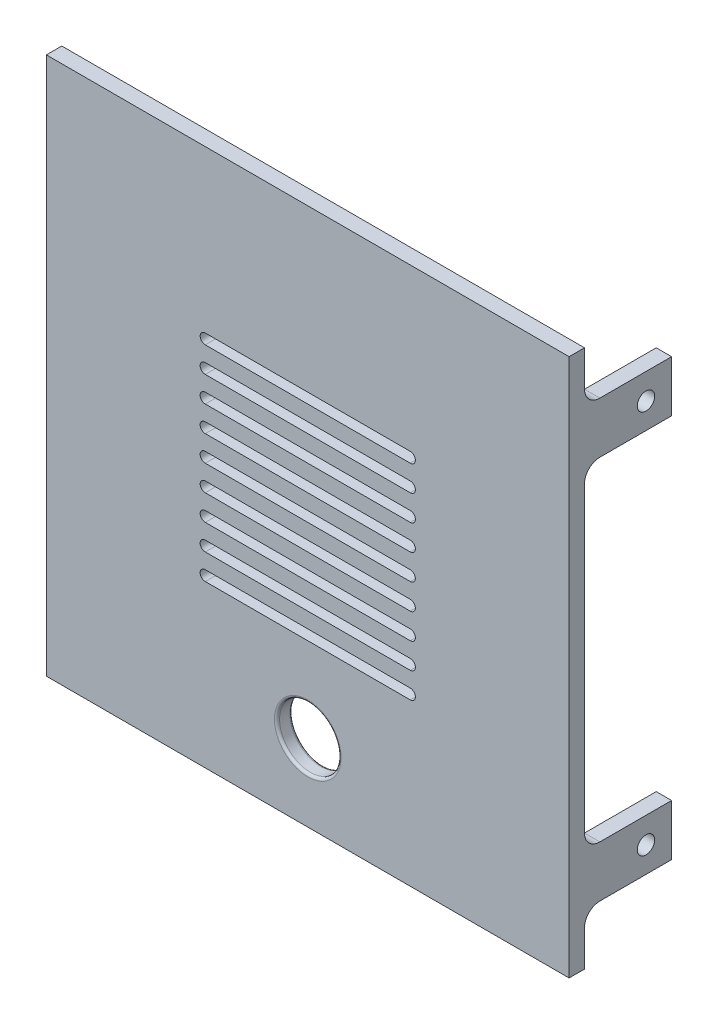
SolidWorks part; units mm, degrees
ref_plane "Front Plane" through (0, 0, 0) normal (0, 0, 1) x (1, 0, 0)
ref_plane "Top Plane" through (0, 0, 0) normal (0, 1, 0) x (1, 0, 0)
ref_plane "Right Plane" through (0, 0, 0) normal (1, 0, 0) x (0, 0, -1)
sketch "Sketch1" plane through (0, 0, 0) normal (0, 0, 1) x (1, 0, 0)
  line L1 (51, 52.5) -> (-51, 52.5)
  line L2 (51, 52.5) -> (51, -52.5)
  line L3 (51, -52.5) -> (-51, -52.5)
  line L4 (-51, 52.5) -> (-51, -52.5)
  line L5 (51, 52.5) -> (-51, -52.5) construction
  line L6 (51, -52.5) -> (-51, 52.5) construction
  point P0 (0, 0)
  dimension "D1" = 105
  dimension "D2" = 102
extrude "Boss-Extrude1" add sketch "Sketch1" along normal mid plane 3
sketch "Sketch2" plane through (0, 0, -1.5) normal (0, 0, -1) x (-1, 0, 0)
  line L1 (41.07, -29.23) -> (44.07, -29.23)
  line L2 (41.07, -29.23) -> (41.07, -39.23)
  line L3 (41.07, -39.23) -> (44.07, -39.23)
  line L4 (44.07, -29.23) -> (44.07, -39.23)
  line L5 (41.07, -29.23) -> (44.07, -39.23) construction
  line L6 (41.07, -39.23) -> (44.07, -29.23) construction
  line L8 (51, -52.5) -> (-51, -52.5) construction
  line L9 (51, 52.5) -> (51, -52.5) construction
  point P0 (42.57, -34.23)
  dimension "D1" = 10
  dimension "D2" = 3
  dimension "D3" = 18.27
  dimension "D4" = 6.93
extrude "Boss-Extrude2" add sketch "Sketch2" along normal blind 23
fillet "Fillet1" radius 2 2 edges at (-41.07, -34.23, -1.5) (-44.07, -34.23, -1.5)
hole_wizard "M3 Clearance Hole1" positions "Sketch3" profile "Sketch5" hole size "M3" standard "ISO" end condition through all
sketch "Sketch3" plane through (-44.07, 0, 0) normal (-1, 0, 0) x (0, 0, 1)
  line L1 (-1.5, 52.5) -> (-1.5, -52.5) construction
  line L2 (-24.5, -34.23) -> (-22.4759, -34.23) construction
  line L3 (-24.5, -39.23) -> (-24.5, -29.23) construction
  point P0 (-20.5, -34.23)
  dimension "D1" = 19
sketch "Sketch5" plane through (-44.07, -34.23, -20.5) normal (0, 1, 0) x (0, 0, 1)
  line L0 (0, 0) -> (0, 95.07)
  line L1 (0, 95.07) -> (1.7, 95.07)
  line L2 (1.7, 95.07) -> (1.7, 0)
  line L5 (1.7, 0) -> (0, 0)
  line L11 (0, -6.35) -> (0, 107.95) construction
  dimension "Thru Hole Dia." = 3.4
  dimension "Thru Hole Depth" = 95.07
sketch "Sketch6" plane through (0, 0, -1.5) normal (0, 0, -1) x (-1, 0, 0)
  line L1 (-48, -32.5) -> (-51, -32.5)
  line L2 (-48, -32.5) -> (-48, -42.5)
  line L3 (-48, -42.5) -> (-51, -42.5)
  line L4 (-51, -32.5) -> (-51, -42.5)
  line L5 (-48, -32.5) -> (-51, -42.5) construction
  line L6 (-48, -42.5) -> (-51, -32.5) construction
  line L7 (51, -52.5) -> (-51, -52.5) construction
  line L8 (-51, -52.5) -> (-51, 52.5) construction
  point P0 (-49.5, -37.5)
  dimension "D1" = 0
  dimension "D2" = 3
  dimension "D3" = 10
  dimension "D4" = 15
extrude "Boss-Extrude3" add sketch "Sketch6" along normal blind 17
hole_wizard "M3 Clearance Hole2" positions "Sketch7" profile "Sketch8" hole size "M3" standard "ISO" end condition up to next
sketch "Sketch7" plane through (51, 0, 0) normal (1, 0, 0) x (0, 0, -1)
  line L0 (-1.5, -52.5) -> (-1.5, 52.5) construction
  line L1 (18.5, -37.5) -> (15.1679, -37.5) construction
  line L2 (18.5, -32.5) -> (18.5, -42.5) construction
  point P0 (13.5, -37.5)
  dimension "D1" = 15
sketch "Sketch8" plane through (51, -37.5, -13.5) normal (0, 1, 0) x (0, 0, -1)
  line L0 (0, 0) -> (0, 3)
  line L1 (0, 3) -> (1.7, 3)
  line L2 (1.7, 3) -> (1.7, 0)
  line L5 (1.7, 0) -> (0, 0)
  line L11 (0, -6.35) -> (0, 107.95) construction
  dimension "Thru Hole Dia." = 3.4
  dimension "Thru Hole Depth" = 3
sketch "Sketch9" plane through (0, 0, 1.5) normal (0, 0, 1) x (1, 0, 0)
  line L0 (-20, 5) -> (20, 5) construction
  line L1 (20, 25) -> (-20, 25) construction
  line L2 (20, 25) -> (20, -25) construction
  line L3 (20, -25) -> (-20, -25) construction
  line L4 (-20, 25) -> (-20, -25) construction
  line L5 (20, 25) -> (-20, -25) construction
  line L6 (20, -25) -> (-20, 25) construction
  line L7 (-20, 6) -> (20, 6)
  line L8 (-20, 4) -> (20, 4)
  line L9 (-20, 0) -> (20, 0) construction
  line L10 (-20, 1) -> (20, 1)
  line L11 (-20, -1) -> (20, -1)
  line L12 (-20, -5) -> (20, -5) construction
  line L13 (-20, -4) -> (20, -4)
  line L14 (-20, -6) -> (20, -6)
  line L15 (-20, 10) -> (20, 10) construction
  line L16 (-20, 11) -> (20, 11)
  line L17 (-20, 9) -> (20, 9)
  line L18 (-20, -10) -> (20, -10) construction
  line L19 (-20, -9) -> (20, -9)
  line L20 (-20, -11) -> (20, -11)
  line L21 (-20, 15) -> (20, 15) construction
  line L22 (-20, 16) -> (20, 16)
  line L23 (-20, 14) -> (20, 14)
  line L24 (-20, 20) -> (20, 20) construction
  line L25 (-20, 21) -> (20, 21)
  line L26 (-20, 19) -> (20, 19)
  line L27 (-20, -15) -> (20, -15) construction
  line L28 (-20, -14) -> (20, -14)
  line L29 (-20, -16) -> (20, -16)
  line L30 (-20, -20) -> (20, -20) construction
  line L31 (-20, -19) -> (20, -19)
  line L32 (-20, -21) -> (20, -21)
  arc A0 (-20, 6) -> (-20, 4) centre (-20, 5) ccw
  arc A1 (20, 4) -> (20, 6) centre (20, 5) ccw
  arc A2 (-20, 1) -> (-20, -1) centre (-20, 0) ccw
  arc A3 (20, -1) -> (20, 1) centre (20, 0) ccw
  arc A4 (-20, -4) -> (-20, -6) centre (-20, -5) ccw
  arc A5 (20, -6) -> (20, -4) centre (20, -5) ccw
  arc A6 (-20, 11) -> (-20, 9) centre (-20, 10) ccw
  arc A7 (20, 9) -> (20, 11) centre (20, 10) ccw
  arc A8 (-20, -9) -> (-20, -11) centre (-20, -10) ccw
  arc A9 (20, -11) -> (20, -9) centre (20, -10) ccw
  arc A10 (-20, 16) -> (-20, 14) centre (-20, 15) ccw
  arc A11 (20, 14) -> (20, 16) centre (20, 15) ccw
  arc A12 (-20, 21) -> (-20, 19) centre (-20, 20) ccw
  arc A13 (20, 19) -> (20, 21) centre (20, 20) ccw
  arc A14 (-20, -14) -> (-20, -16) centre (-20, -15) ccw
  arc A15 (20, -16) -> (20, -14) centre (20, -15) ccw
  arc A16 (-20, -19) -> (-20, -21) centre (-20, -20) ccw
  arc A17 (20, -21) -> (20, -19) centre (20, -20) ccw
  point P0 (0, 0)
  point P8 (0, 5)
  point P14 (0, 0)
  point P23 (0, -5)
  point P30 (0, 10)
  point P35 (0, -10)
  point P44 (0, 15)
  point P49 (0, 20)
  point P56 (0, -15)
  point P63 (0, -20)
  dimension "D1" = 40
  dimension "D2" = 50
  dimension "D3" = 2
  dimension "D4" = 2
  dimension "D5" = 5
  dimension "D6" = 2
  dimension "D7" = 5
  dimension "D8" = 2
  dimension "D9" = 2
  dimension "D10" = 10
  dimension "D11" = 10
  dimension "D12" = 2
  dimension "D13" = 2
  dimension "D14" = 2
  dimension "D15" = 2
  dimension "D16" = 15
  dimension "D17" = 20
  dimension "D18" = 15
  dimension "D19" = 20
extrude "Cut-Extrude1" cut sketch "Sketch9" against normal blind 10
sketch "Sketch10" plane through (0, 0, -1.5) normal (0, 0, -1) x (-1, 0, 0)
  line L0 (51, -52.5) -> (-51, -52.5) construction
  line L2 (0, 0) -> (0, 14) construction
  line L3 (-20, 14) -> (20, 14) construction
  circle A0 centre (0, -37.5) radius 6
  dimension "D1" = 12
  dimension "D2" = 15
extrude "Cut-Extrude2" cut sketch "Sketch10" against normal blind 10
mirror "Mirror1" about plane through (0, 0, 0) normal (0, 1, 0) of "M3 Clearance Hole2", "Boss-Extrude3"
fillet "Fillet2" radius 3 8 edges at (49.5, -42.5, -1.5) (49.5, -32.5, -1.5) (48, -37.5, -1.5) (-42.57, -39.23, -1.5) (-42.57, -29.23, -1.5) (49.5, 42.5, -1.5) (48, 37.5, -1.5) (49.5, 32.5, -1.5)
fillet "Fillet3" radius 0.5 2 edges at (-6, -37.5, 1.5) (-6, -37.5, -1.5)
